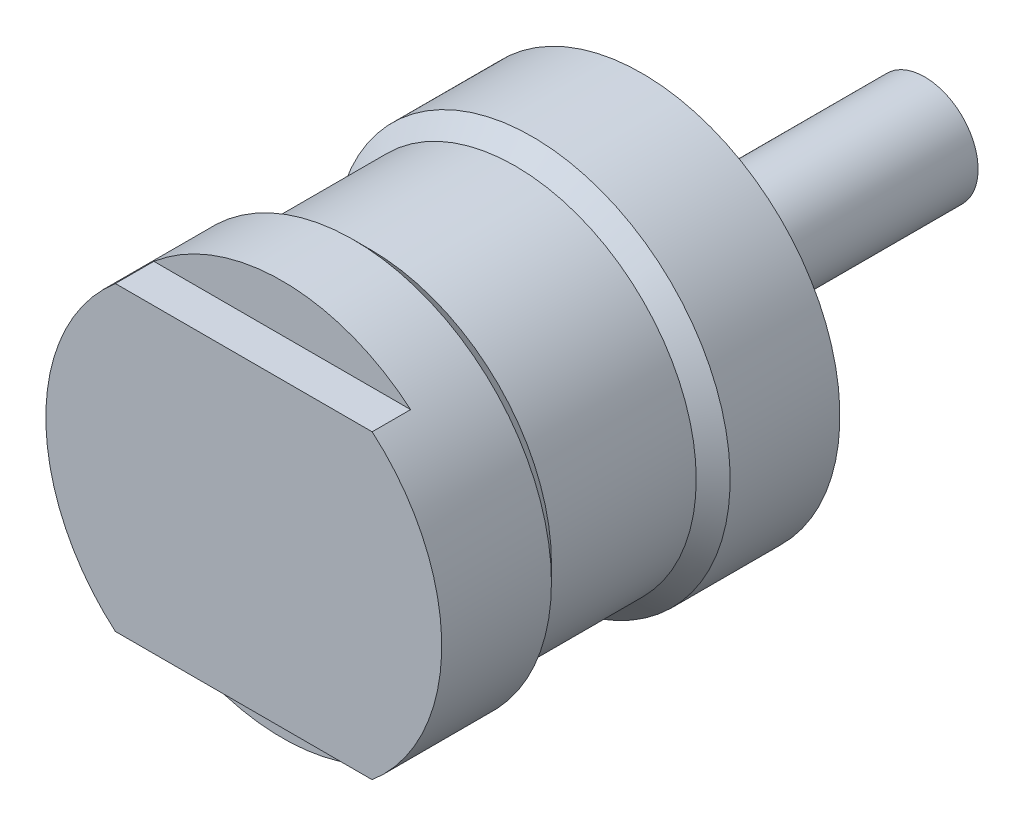
SolidWorks part; units mm, degrees
ref_plane "Front Plane" through (0, 0, 0) normal (0, 0, 1) x (1, 0, 0)
ref_plane "Top Plane" through (0, 0, 0) normal (0, 1, 0) x (1, 0, 0)
ref_plane "Right Plane" through (0, 0, 0) normal (1, 0, 0) x (0, 0, -1)
sketch "Sketch1" plane through (0, 0, 0) normal (0, 0, 1) x (1, 0, 0)
  circle A0 centre (0, 0) radius 11.1125
  dimension "D1" = 22.225
extrude "Boss-Extrude1" add sketch "Sketch1" along normal blind 6.096
sketch "Sketch2" plane through (0, 0, 6.096) normal (0, 0, 1) x (1, 0, 0)
  circle A0 centre (0, 0) radius 10.16
  dimension "D1" = 20.32
extrude "Boss-Extrude2" add sketch "Sketch2" along normal blind 10.16
sketch "Sketch3" plane through (0, 0, 16.256) normal (0, 0, 1) x (1, 0, 0)
  circle A0 centre (0, 0) radius 11.1125
  circle A1 centre (0, 0) radius 11.1125 construction
extrude "Boss-Extrude3" add sketch "Sketch3" along normal blind 6.096
sketch "Sketch4" plane through (0, 0, 22.352) normal (0, 0, 1) x (1, 0, 0)
  line L1 (-17.2623, 8.4582) -> (14.8583, 8.4582)
  line L2 (-17.2623, 8.4582) -> (-17.2623, -8.4582)
  line L3 (-17.2623, -8.4582) -> (14.8583, -8.4582)
  line L4 (14.8583, 8.4582) -> (14.8583, -8.4582)
  circle A0 centre (0, 0) radius 11.1125
  circle M1 centre (0, 0) radius 11.1125
  dimension "D1" = 16.9164
  dimension "D2" = 8.4582
extrude "Cut-Extrude1" cut sketch "Sketch4" against normal blind 2.159 contours L1 M1 | L3 M1 region at (0, 9.5316, 22.352) region at (0, -9.5316, 22.352)
chamfer "Chamfer1" distance 1.016 angle 45 2 edges at (10.16, 0, 6.096) (10.16, 0, 16.256)
sketch "Sketch5" plane through (0, 0, 0) normal (0, 0, -1) x (-1, 0, 0)
  circle A0 centre (0, 0) radius 5.08
  dimension "D1" = 10.16
extrude "Boss-Extrude4" add sketch "Sketch5" along normal blind 0.762
sketch "Sketch6" plane through (0, 0, -0.762) normal (0, 0, -1) x (-1, 0, 0)
  circle A0 centre (0, 0) radius 3.937
  dimension "D1" = 7.874
extrude "Boss-Extrude5" add sketch "Sketch6" along normal blind 1.778
sketch "Sketch7" plane through (0, 0, -2.54) normal (0, 0, -1) x (-1, 0, 0)
  circle A0 centre (0, 0) radius 2.9972
  dimension "D1" = 5.9944
extrude "Boss-Extrude6" add sketch "Sketch7" along normal blind 13.335
sketch "Sketch8" plane through (0, 0, 0) normal (0, 0, -1) x (-1, 0, 0)
  line L1 (7, 0) -> (-3.5, 6.0622) construction
  line L2 (-3.5, 6.0622) -> (-3.5, -6.0622) construction
  line L3 (-3.5, -6.0622) -> (7, 0) construction
  circle A0 centre (0, 0) radius 7 construction
  circle A1 centre (7, 0) radius 1.25
  circle A2 centre (-3.5, -6.0622) radius 1.25
  circle A3 centre (-3.5, 6.0622) radius 1.25
  dimension "D1" = 14
  dimension "D2" = 2.5
extrude "Cut-Extrude2" cut sketch "Sketch8" against normal blind 7.747
